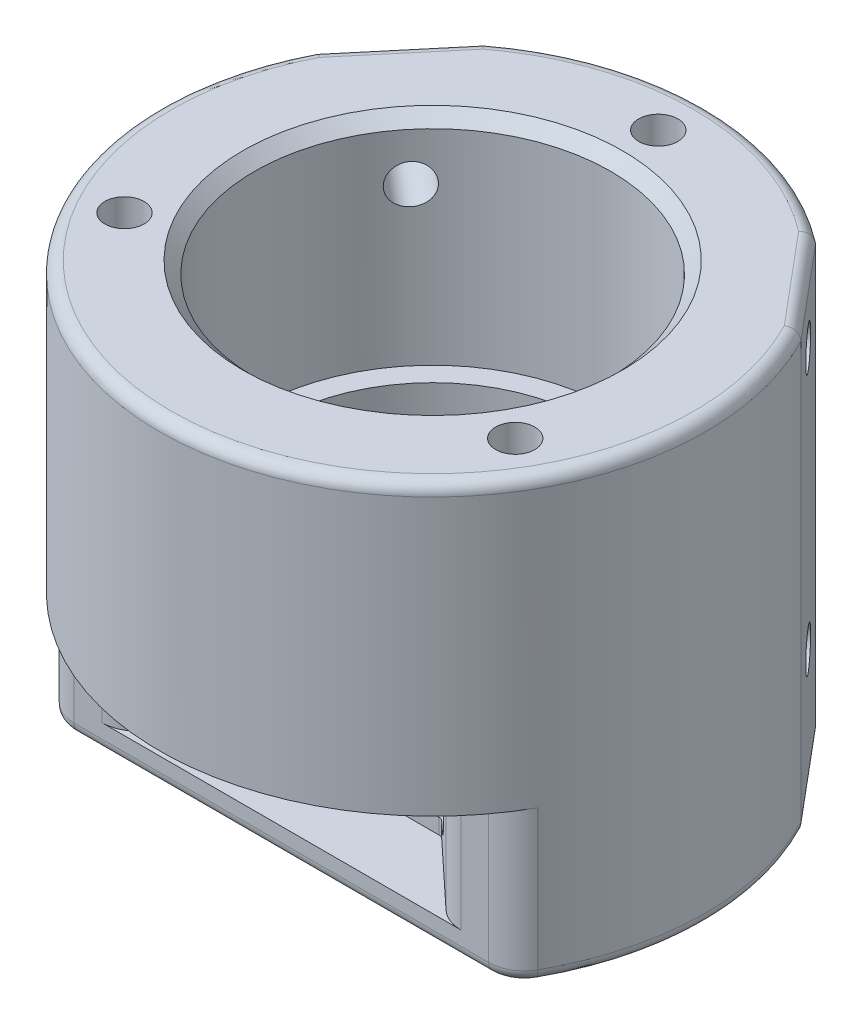
SolidWorks part; units mm, degrees
material "6061-T6 (SS)"
ref_plane "Front Plane" through (0, 0, 0) normal (0, 0, 1) x (1, 0, 0)
ref_plane "Top Plane" through (0, 0, 0) normal (0, 1, 0) x (1, 0, 0)
ref_plane "Right Plane" through (0, 0, 0) normal (1, 0, 0) x (0, 0, -1)
sketch "Sketch1" plane through (0, 0, 0) normal (1, 0, 0) x (0, 0, -1)
  line L0 (0, 0) -> (0, 62021.3178) construction
  line L1 (13.2, 3.5) -> (13.2, 18.844)
  line L2 (13.2, 18.844) -> (15, 18.844)
  line L3 (23, 16.0132) -> (23, 0)
  line L4 (8.5, 0) -> (5.5, 0)
  line L5 (13.2, 3.5) -> (3.75, 3.5)
  line L6 (3.75, 3.5) -> (3.75, 1.35)
  line L7 (15, 18.844) -> (15, 37.094)
  line L8 (5.5, 0) -> (5.5, 1.35)
  line L9 (5.5, 1.35) -> (3.75, 1.35)
  line L10 (15, 37.094) -> (23, 37.094)
  line L11 (23, 37.094) -> (23, 16.0132)
  line L12 (8.5, 0) -> (23, 0)
  dimension "D1" = 13.2
  dimension "D2" = 23
  dimension "D3" = 18.844
  dimension "D4" = 3.75
  dimension "D5" = 3.5
  dimension "D6" = 1.35
  dimension "D7" = 5.5
  dimension "D8" = 18.25
  dimension "D9" = 15
revolve "Revolve1" add sketch "Sketch1" angle 360 about L0
hole_wizard "CSK for M2 Countersunk Flat Head Screw1" positions "Sketch3" profile "Sketch2" countersink size "M2" standard "DIN" end condition through all
sketch "Sketch3" plane through (0, 3.5, 0) normal (0, 1, 0) x (1, 0, 0)
  line L0 (-5.6292, -3.25) -> (0, 0) construction
  line L1 (0, 0) -> (0, 6.5) construction
  line L3 (0, 0) -> (5.6292, -3.25) construction
  circle A0 centre (0, 0) radius 6.5 construction
  point P0 (0, 6.5)
  point P2 (-5.6292, -3.25)
  point P4 (5.6292, -3.25)
  dimension "D1" = 13
  dimension "D2" = 120
  dimension "D3" = 120
sketch "Sketch2" plane through (0, 3.5, -6.5) normal (1, 0, 0) x (0, 0, 1)
  line L0 (0, 0) -> (0, 3.5)
  line L1 (0, 3.5) -> (1.1, 3.5)
  line L2 (1.1, 3.5) -> (1.1, 1.1)
  line L3 (1.1, 1.1) -> (2.2, 0)
  line L5 (2.2, 0) -> (0, 0)
  line L6 (-1.1, 1.1) -> (-2.2, 0) construction
  line L11 (0, -6.35) -> (0, 107.95) construction
  dimension "Thru Hole Dia." = 2.2
  dimension "Thru Hole Depth" = 3.5
  dimension "Near C'Sink Dia." = 4.4
  dimension "Near C'Sink Angle" = 90
sketch "Sketch5" plane through (0, 3.5, 0) normal (0, 1, 0) x (1, 0, 0)
  line L0 (-10.4775, -15.748) -> (10.4775, -15.748) construction
  line L1 (0, -15.748) -> (0, 0) construction
  line L2 (-13.5, -29.563) -> (13.5, -29.563)
  line L3 (13.5, -29.563) -> (13.5, -18.6212)
  line L4 (13.9342, -12.748) -> (7.5, -6.748)
  line L5 (7.5, -6.748) -> (-7.5, -6.748)
  line L6 (-7.5, -6.748) -> (-13.9342, -12.748)
  line L7 (-13.5, -29.563) -> (-13.5, -18.6212)
  line L8 (-13.9342, -12.748) -> (-19.1439, -12.748)
  line L9 (13.9342, -12.748) -> (19.1439, -12.748)
  arc A0 (-19.1439, -12.748) -> (-13.5, -18.6212) centre (0, 0) ccw
  circle A1 centre (0, 0) radius 15
  circle A2 centre (0, 0) radius 15
  circle A3 centre (0, 0) radius 23 construction
  arc A4 (-19.1439, -12.748) -> (-13.5, -18.6212) centre (0, 0) ccw
  arc A5 (13.5, -18.6212) -> (19.1439, -12.748) centre (0, 0) ccw
  circle M13 centre (0, 0) radius 13.2
  dimension "D1" = 15.748
  dimension "D2" = 20.955
  dimension "D3" = 27
  dimension "D4" = 133
  dimension "D5" = 9
  dimension "D6" = 15
  dimension "D7" = 0
  dimension "D8" = 6
extrude "Cut-Extrude1" cut sketch "Sketch5" along normal blind 9.319 and the other way blind 1.3 contours L3 A5 L9 L4 A2 L6 L8 A0 L7 L2 | L5 L6 L4 M13 | L6 A2 L4 M13
fillet "Fillet1" radius 3 4 edges at (-19.1439, 7.5095, 12.748) (-13.9342, 7.5095, 12.748) (13.9342, 7.5095, 12.748) (19.1439, 7.5095, 12.748)
fillet "Fillet2" radius 2 1 edges at (0, 3.5, -13.2)
sketch "Sketch14" plane through (0, 0, 0) normal (0, -1, 0) x (1, 0, 0)
  line L0 (1.1, -6.5) -> (1.1, -5.3889)
  line L1 (-1.1, -6.5) -> (-1.1, -5.3889)
  line L2 (-6.1792, 2.2974) -> (-5.2169, 1.7418)
  line L3 (-5.0792, 4.2026) -> (-4.1169, 3.6471)
  line L4 (5.0792, 4.2026) -> (4.1169, 3.6471)
  line L5 (6.1792, 2.2974) -> (5.2169, 1.7418)
  line L6 (0, 0) -> (1.1, -1.8482) construction
  arc A0 (-1.1, -6.5) -> (1.1, -6.5) centre (0, -6.5) ccw
  arc A1 (-0.4212, -5.4838) -> (0.4212, -5.4838) centre (0, -6.5) ccw construction
  arc A2 (-5.0792, 4.2026) -> (-6.1792, 2.2974) centre (-5.6292, 3.25) ccw
  arc A3 (6.1792, 2.2974) -> (5.0792, 4.2026) centre (5.6292, 3.25) ccw
  arc A4 (4.1169, 3.6471) -> (-4.1169, 3.6471) centre (0, 0) ccw
  arc A5 (0.4212, -5.4838) -> (4.9598, 2.3771) centre (0, 0) ccw construction
  arc A6 (-5.2169, 1.7418) -> (-1.1, -5.3889) centre (0, 0) ccw
  arc A7 (1.1, -5.3889) -> (5.2169, 1.7418) centre (0, 0) ccw
  dimension "D1" = 3
  dimension "D2" = 2.1507
extrude "Cut-Extrude3" cut sketch "Sketch14" against normal up to surface (1.35 mm away) up to face at (0, 1.35, 0)
hole_wizard "M4 Tapped Hole2" positions "Sketch7" profile "Sketch8" tap size "M4" standard "DIN"
sketch "Sketch7" plane through (0, 37.094, 0) normal (0, -1, 0) x (-1, 0, 0)
  line L0 (-16.4545, -9.5) -> (0, 0) construction
  line L1 (0, 0) -> (16.4545, -9.5) construction
  line L3 (0, 0) -> (0, 19) construction
  point P0 (16.4545, -9.5)
  point P2 (0, 19)
  point P4 (-16.4545, -9.5)
  dimension "D1" = 120
  dimension "D2" = 120
  dimension "D3" = 19
cosmetic thread "Hole Thread7" parameters "D1"=8, "D2"=4
cosmetic thread "Hole Thread8" parameters "D1"=8, "D2"=4
cosmetic thread "Hole Thread9" parameters "D1"=8, "D2"=4
sketch "Sketch8" plane through (-16.4545, 37.094, 9.5) normal (1, 0, 0) x (0, 0, 1)
  line L0 (0, 0) -> (0, 11.0914)
  line L1 (0, 11.0914) -> (1.65, 10.1)
  line L2 (1.65, 10.1) -> (1.65, 0)
  line L5 (1.65, 0) -> (0, 0)
  line L10 (0, 11.0914) -> (-1.65, 10.1) construction
  line L11 (0, -6.35) -> (0, 107.95) construction
  dimension "Tap Drill Dia." = 3.3
  dimension "Tap Drill Depth" = 10.1
  dimension "Drill Angle" = 118
hole_wizard "M2.5 Tapped Hole1" positions "Sketch10" profile "Sketch9" tap size "M2.5" standard "DIN"
sketch "Sketch10" plane through (0, 12.819, 0) normal (0, -1, 0) x (-1, 0, 0)
  line L0 (-10.4775, -15.748) -> (10.4775, -15.748) construction
  line L2 (0, -15.748) -> (0, 0) construction
  point P0 (-10.4775, -15.748)
  point P3 (10.4775, -15.748)
  dimension "D1" = 15.748
  dimension "D2" = 20.955
sketch "Sketch9" plane through (10.4775, 12.819, 15.748) normal (1, 0, 0) x (0, 0, -1)
  line L0 (0, 0) -> (0, 6.9659)
  line L1 (0, 6.9659) -> (1.025, 6.35)
  line L2 (1.025, 6.35) -> (1.025, 0)
  line L5 (1.025, 0) -> (0, 0)
  line L10 (0, 6.9659) -> (-1.025, 6.35) construction
  line L11 (0, -6.35) -> (0, 107.95) construction
  dimension "Tap Drill Dia." = 2.05
  dimension "Tap Drill Depth" = 6.35
  dimension "Drill Angle" = 118
cosmetic thread "Hole Thread1" parameters "D1"=5, "D2"=2.5
cosmetic thread "Hole Thread2" parameters "D1"=5, "D2"=2.5
sketch "Sketch15" plane through (0, 0, 0) normal (0, -1, 0) x (1, 0, 0)
  line L1 (15.1159, 12.748) -> (17.4636, 12.748) construction
  line L4 (-15.1159, 12.748) -> (-17.4636, 12.748) construction
  line L5 (15.1159, 12.748) -> (17.4636, 12.748)
  line L6 (-15.1159, 12.748) -> (-17.4636, 12.748)
  line L7 (-15.1159, 12.748) -> (15.1159, 12.748)
  circle A0 centre (-10.4775, 15.748) radius 1.025 construction
  circle A1 centre (-10.4775, 15.748) radius 1.025 construction
  circle A2 centre (10.4775, 15.748) radius 1.025 construction
  circle A3 centre (10.4775, 15.748) radius 1.025 construction
  circle A6 centre (0, 0) radius 23
  arc A7 (20.0831, 11.2102) -> (-20.0831, 11.2102) centre (0, 0) ccw
  arc A11 (20.0831, 11.2102) -> (17.4636, 12.748) centre (17.4636, 9.748) ccw construction
  arc A14 (-17.4636, 12.748) -> (-20.0831, 11.2102) centre (-17.4636, 9.748) ccw construction
  arc A15 (20.0831, 11.2102) -> (17.4636, 12.748) centre (17.4636, 9.748) ccw
  arc A18 (-17.4636, 12.748) -> (-20.0831, 11.2102) centre (-17.4636, 9.748) ccw
  dimension "D2" = 0
extrude "Cut-Extrude4" cut sketch "Sketch15" against normal up to next
sketch "Sketch11" plane through (0, 0, 0) normal (0, 1, 0) x (1, 0, 0)
  line L0 (-20.4116, 10.6003) -> (-13.9837, 18.2608)
  line L1 (13.9837, 18.2608) -> (20.4116, 10.6003)
  line L2 (0, 0) -> (0, 50000) construction
  line L3 (-17.1977, 14.4305) -> (0, 0) construction
  arc A0 (-20.4116, 10.6003) -> (20.4116, 10.6003) centre (0, 0) ccw
  arc A1 (13.9837, 18.2608) -> (-13.9837, 18.2608) centre (0, 0) ccw
  circle A2 centre (0, 0) radius 23 construction
  dimension "D1" = 10
  dimension "D2" = 50
extrude "Cut-Extrude2" cut sketch "Sketch11" along normal through all flip side to cut contours L1 A1 L0 A0
fillet "Fillet3" radius 1 12 edges at (0, 0, 12.748) (-18.9824, 0, 12.3351) (18.9824, 0, 12.3351) (22.9974, 0, 0.3464) (-22.9974, 0, 0.3464) (0, 37.094, 23) (0, 37.094, -23) (0, 0, -23) (-17.1977, 37.094, -14.4305) (17.1977, 37.094, -14.4305) (17.1977, 0, -14.4305) (-17.1977, 0, -14.4305)
chamfer "Chamfer1" distance 1 angle 45 1 edges at (0, 37.094, -15)
hole_wizard "M4 Tapped Hole1" positions "Sketch13" profile "Sketch12" tap size "M4" standard "DIN"
sketch "Sketch13" plane through (17.1977, 0, -14.4305) normal (0.766, 0, -0.6428) x (-0.6428, 0, -0.766)
  line L0 (5, 37.094) -> (-5, 37.094) construction
  point P0 (0, 10.094)
  point P10 (0, 32.094)
  dimension "D1" = 27
  dimension "D2" = 5
sketch "Sketch12" plane through (17.1977, 10.094, -14.4305) normal (0, 1, 0) x (-0.6428, 0, -0.766)
  line L0 (0, 0) -> (0, 11.0914)
  line L1 (0, 11.0914) -> (1.65, 10.1)
  line L2 (1.65, 10.1) -> (1.65, 0)
  line L5 (1.65, 0) -> (0, 0)
  line L10 (0, 11.0914) -> (-1.65, 10.1) construction
  line L11 (0, -6.35) -> (0, 107.95) construction
  dimension "Tap Drill Dia." = 3.3
  dimension "Tap Drill Depth" = 10.1
  dimension "Drill Angle" = 118
cosmetic thread "Hole Thread3" parameters "D1"=8, "D2"=4
cosmetic thread "Hole Thread10" parameters "D1"=8, "D2"=4
mirror "Mirror1" about plane through (0, 0, 0) normal (1, 0, 0) of "M4 Tapped Hole1"
fillet "Fillet4" radius 0.5 2 edges at (7.5, 2.85, 6.748) (-7.5, 2.85, 6.748)
